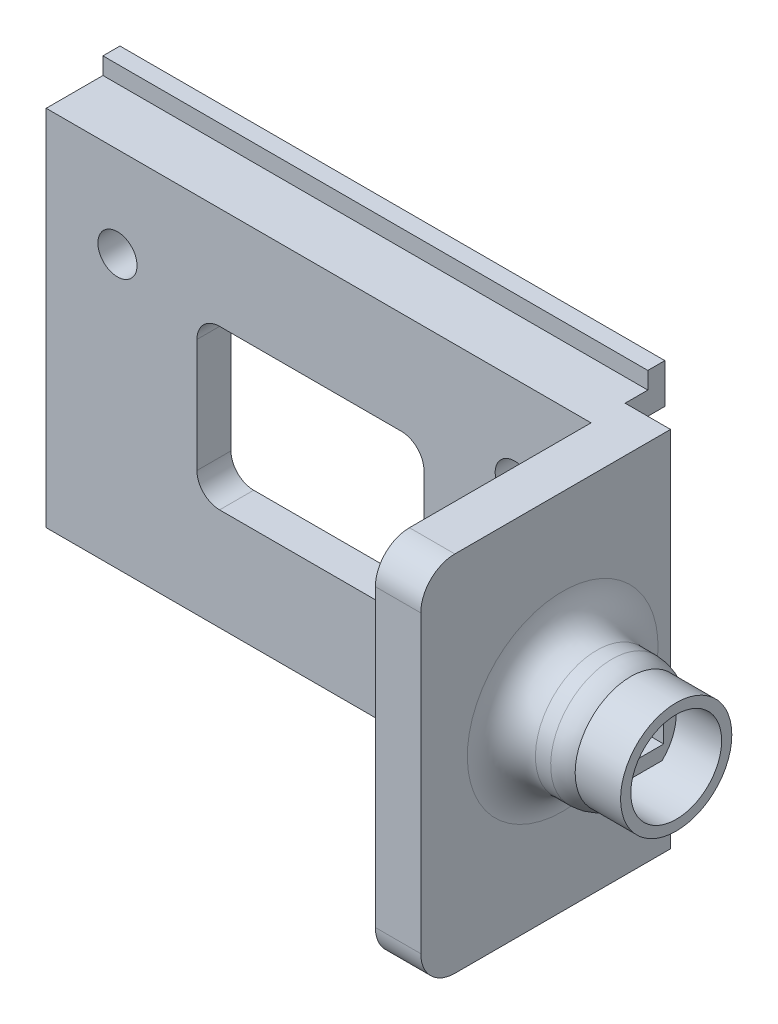
SolidWorks part; units mm, degrees
ref_plane "Front Plane" through (0, 0, 0) normal (0, 0, 1) x (1, 0, 0)
ref_plane "Top Plane" through (0, 0, 0) normal (0, 1, 0) x (1, 0, 0)
ref_plane "Right Plane" through (0, 0, 0) normal (1, 0, 0) x (0, 0, -1)
sketch "Sketch1" plane through (0, 0, 0) normal (0, 0, 1) x (1, 0, 0)
  line L1 (0, 0) -> (52, 0)
  line L2 (0, 0) -> (0, -32)
  line L3 (0, -32) -> (52, -32)
  line L4 (52, 0) -> (52, -32)
  dimension "D1" = 52
  dimension "D2" = 32
extrude "Boss-Extrude1" add sketch "Sketch1" along normal blind 3
ref_plane "Plane1" through (0, 0, 2) normal (0, 0, -1) x (-1, 0, 0)
sketch "Sketch2" plane through (0, 0, 2) normal (0, 0, -1) x (-1, 0, 0)
  line L1 (-48, 0) -> (-52, 0)
  line L2 (-48, 0) -> (-48, -32)
  line L3 (-48, -32) -> (-52, -32)
  line L4 (-52, 0) -> (-52, -32)
  dimension "D1" = 4
extrude "Boss-Extrude2" add sketch "Sketch2" against normal blind 20
fillet "Fillet1" radius 3 2 edges at (50, -32, 22) (50, 0, 22)
sketch "Sketch4" plane through (0, 0, 3) normal (0, 0, 1) x (1, 0, 0)
  line L0 (48, 0) -> (0, 0) construction
  circle A0 centre (41.2777, -8) radius 1.725
  circle A1 centre (6.2777, -8) radius 1.725
  dimension "D1" = 35
  dimension "D2" = 8
  dimension "D3" = 8
extrude "Cut-Extrude2" cut sketch "Sketch4" against normal up to surface (3 mm away) up to face at (26, -16, 0)
sketch "Sketch6" plane through (0, 0, 3) normal (0, 0, 1) x (1, 0, 0)
  line L0 (48, 0) -> (0, 0) construction
  line L1 (33.2777, -9) -> (13.2777, -9)
  line L2 (33.2777, -9) -> (33.2777, -23)
  line L3 (33.2777, -23) -> (13.2777, -23)
  line L4 (13.2777, -9) -> (13.2777, -23)
  circle A0 centre (6.2777, -8) radius 1.725 construction
  dimension "D3" = 7
  dimension "D1" = 14
  dimension "D2" = 20
  dimension "D4" = 9
extrude "Cut-Extrude3" cut sketch "Sketch6" against normal up to surface (3 mm away) up to face at (43.0027, -8, 0)
sketch "Sketch7" plane through (52, 0, 0) normal (1, 0, 0) x (0, 0, -1)
  line L0 (-22, -16) -> (2.0181, -16) construction
  line L1 (-12.4, -17.7) -> (-6.6, -17.7)
  line L2 (-12.4, -17.7) -> (-12.4, -14.3)
  line L3 (-12.4, -14.3) -> (-6.6, -14.3)
  line L4 (-6.6, -17.7) -> (-6.6, -14.3)
  line L5 (-22, -3) -> (-22, -29) construction
  line L6 (-9.5, -32) -> (-9.5, 5.4647) construction
  line L7 (-19, -32) -> (0, -32) construction
  line L8 (-13.6, -13.1) -> (-5.4, -13.1)
  line L9 (-5.4, -18.9) -> (-5.4, -13.1)
  line L10 (-13.6, -18.9) -> (-5.4, -18.9)
  line L11 (-13.6, -18.9) -> (-13.6, -13.1)
  dimension "D5" = 1.2
  dimension "D1" = 5.8
  dimension "D2" = 3.4
  dimension "D3" = 1.7
  dimension "D4" = 2.9
sketch "Sketch8" plane through (52, 0, 0) normal (1, 0, 0) x (0, 0, -1)
  line L0 (-9.5, -16) -> (-9.5, 10.2333) construction
  line L1 (-22, -16) -> (3, -16) construction
  line L3 (0, -32) -> (0, 0) construction
  line L6 (-19, -32) -> (0, -32) construction
  circle A0 centre (-9.5, -16) radius 4.25
  circle A1 centre (-9.5, -16) radius 5.4
  dimension "D1" = 10.8
  dimension "D2" = 8.5
  dimension "D3" = 9.5
  dimension "D4" = 16
extrude "Boss-Extrude4" add sketch "Sketch7" along normal blind 6
sketch "Sketch10" plane through (52, 0, 0) normal (1, 0, 0) x (0, 0, -1)
  line L0 (-19, -32) -> (0, -32) construction
  line L1 (0, -32) -> (0, 0) construction
  circle A0 centre (-9.5, -16) radius 4
  circle A1 centre (-9.5, -16) radius 4.9
  dimension "D1" = 9.8
  dimension "D2" = 8
  dimension "D3" = 16
  dimension "D4" = 9.5
extrude "Boss-Extrude6" add sketch "Sketch10" along normal blind 10
extrude "Boss-Extrude5" add sketch "Sketch8" along normal blind 6
fillet "Fillet2" radius 2 4 edges at (13.2777, -9, 1.5) (13.2777, -23, 1.5) (33.2777, -9, 1.5) (33.2777, -23, 1.5)
fillet "Fillet3" radius 3 2 edges at (52, -21.4, 9.5) (58, -16, 4.1)
sketch "Sketch15" plane through (0, 0, 0) normal (-1, 0, 0) x (0, 0, 1)
  line L1 (3, -32) -> (0, -32) construction
  line L6 (-3.5, -2) -> (-3.5, 1.5)
  line L8 (0, -16) -> (-8.2188, -16) construction
  line L9 (0, 0) -> (0, -32) construction
  line L17 (0, -2) -> (-3.5, -2)
  line L23 (-3.5, -33.5) -> (-2, -33.5)
  line L24 (-3.5, -30) -> (-3.5, -33.5)
  line L25 (0, -30) -> (-3.5, -30)
  line L26 (0, -32) -> (0, -30)
  line L27 (-2, -32) -> (0, -32)
  line L28 (-2, -33.5) -> (-2, -32)
  line L29 (0, 0) -> (0, -2)
  line L30 (-2, 0) -> (0, 0)
  line L31 (-2, 1.5) -> (-2, 0)
  line L32 (-3.5, 1.5) -> (-2, 1.5)
  dimension "D1" = 2
  dimension "D2" = 2
  dimension "D3" = 3.5
extrude "Boss-Extrude7" add sketch "Sketch15" against normal up to surface (48 mm away) up to face at (48, -16, 14.8738)
sketch "Sketch16" plane through (0, 0, 2) normal (0, 0, -1) x (-1, 0, 0)
  line L0 (0, -16) -> (-52, -16) construction
  line L1 (0, -2) -> (0, -30) construction
  line L2 (-52, -32) -> (-52, 0) construction
  line L3 (-26, -16) -> (-26, 2.5712) construction
